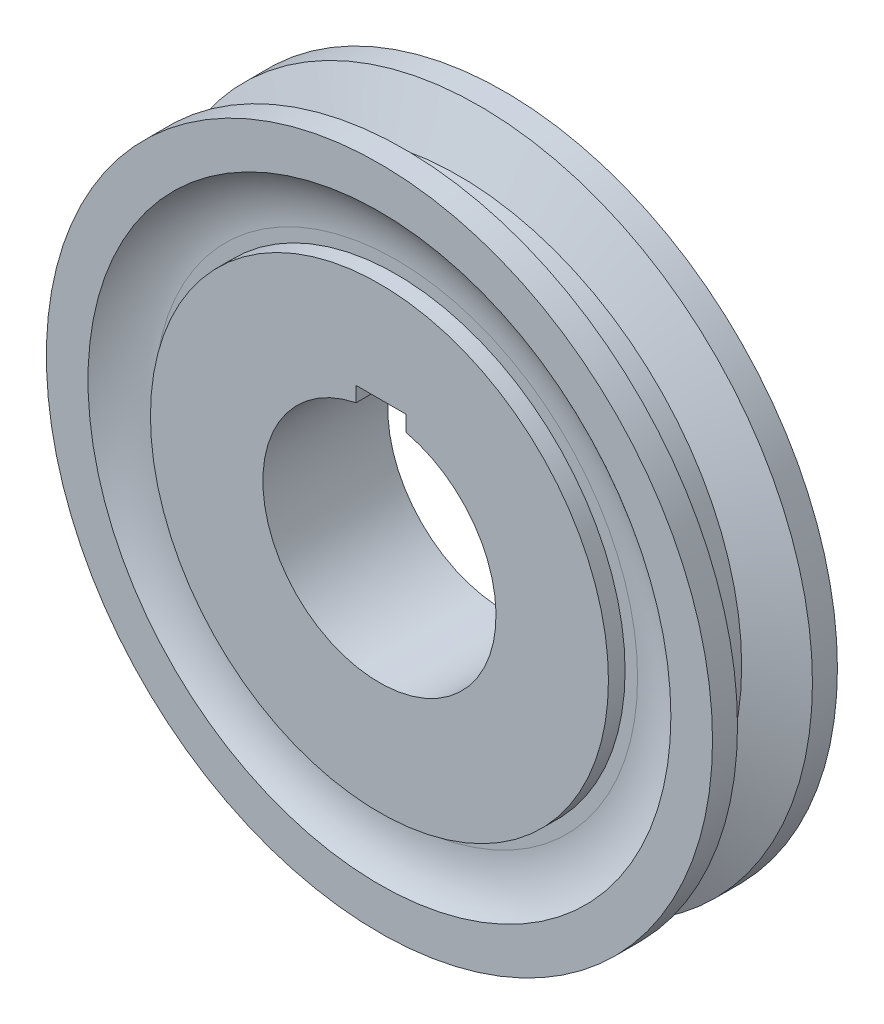
SolidWorks part; units mm, degrees
material "Cast Alloy Steel"
ref_plane "Front Plane" through (0, 0, 0) normal (0, 0, 1) x (1, 0, 0)
ref_plane "Top Plane" through (0, 0, 0) normal (0, 1, 0) x (1, 0, 0)
ref_plane "Right Plane" through (0, 0, 0) normal (1, 0, 0) x (0, 0, -1)
sketch "Sketch1" plane through (0, 0, 0) normal (1, 0, 0) x (0, 0, -1)
  line L0 (-652.0037, 0) -> (31948.1822, 0) construction
  line L1 (0, 0) -> (0, 40) construction
  line L2 (4.5, 40) -> (7.5, 40)
  line L3 (7.5, 40) -> (7.5, 0)
  line L4 (7.5, 0) -> (-7.5, 0)
  line L5 (7.5, 40) -> (4.5, 40)
  line L6 (4.5, 40) -> (2, 34)
  line L7 (2, 34) -> (-2, 34)
  line L8 (-4.5, 40) -> (-2, 34)
  line L9 (-7.5, 40) -> (-4.5, 40)
  line L10 (-7.5, 40) -> (-7.5, 0)
  line L11 (-4.5, 40) -> (-7.5, 40)
  point P12 (0, 34)
  dimension "D1" = 7.5
  dimension "D2" = 40
  dimension "D3" = 3
  dimension "D4" = 2
  dimension "D5" = 6
revolve "Revolve1" add sketch "Sketch1" angle 360 about L0 region at (0, 18.7914, 0)
sketch "Sketch2" plane through (0, 0, 7.5) normal (0, 0, 1) x (1, 0, 0)
  line L1 (3.2, 15.5202) -> (-2.8, 15.5202)
  line L2 (3.2, 15.5202) -> (3.2, 13.6294)
  line L4 (-2.8, 15.5202) -> (-2.8, 13.7171)
  arc A0 (-2.8, 13.7171) -> (3.2, 13.6294) centre (0, 0) ccw
  point P3 (0, 14)
  dimension "D1" = 28
  dimension "D2" = 6
  dimension "D3" = 15.5202
  dimension "D4" = 1.8031
extrude "Cut-Extrude1" cut sketch "Sketch2" against normal through all
sketch "Sketch3" plane through (0, 0, 7.5) normal (0, 0, 1) x (1, 0, 0)
  circle A0 centre (0, 0) radius 35
  circle A1 centre (0, 0) radius 27.5
  dimension "D1" = 70
  dimension "D2" = 55
extrude "Cut-Extrude2" cut sketch "Sketch3" against normal blind 2
sketch "Sketch4" plane through (0, 0, -7.5) normal (0, 0, -1) x (-1, 0, 0)
  circle A0 centre (0, 0) radius 35
  circle A1 centre (0, 0) radius 27.5
  dimension "D1" = 70
  dimension "D2" = 55
extrude "Cut-Extrude3" cut sketch "Sketch4" against normal blind 2
fillet "Fillet1" radius 10 1 edges at (35, 0, 5.5)
fillet "Fillet2" radius 10 1 edges at (-27.5, 0, -5.5)
